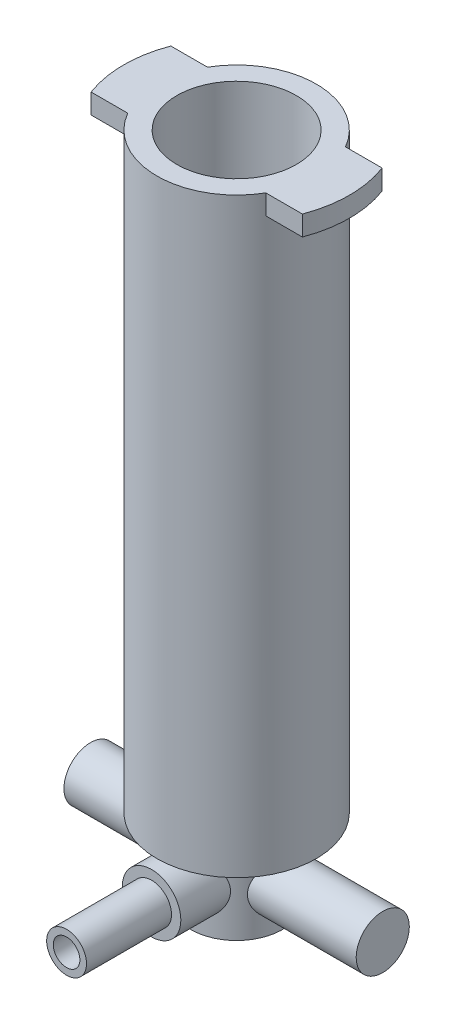
SolidWorks part; units mm, degrees
ref_plane "Front Plane" through (0, 0, 0) normal (0, 0, 1) x (1, 0, 0)
ref_plane "Top Plane" through (0, 0, 0) normal (0, 1, 0) x (1, 0, 0)
ref_plane "Right Plane" through (0, 0, 0) normal (1, 0, 0) x (0, 0, -1)
sketch "Sketch1" plane through (0, 0, 0) normal (0, 1, 0) x (1, 0, 0)
  circle A0 centre (0, 0) radius 6
extrude "Boss-Extrude1" add sketch "Sketch1" along normal blind 44.5
shell "Shell1" thickness 1.5 removed face at (0, 44.5, 6)
sketch "Sketch3" plane through (0, 0, 0) normal (0, -1, 0) x (1, 0, 0)
  circle A0 centre (0, 0) radius 3.45
extrude "Boss-Extrude3" add sketch "Sketch3" along normal blind 5.9
shell "Shell2" thickness 1.5 removed face at (0, 1.5, 4.5)
sketch "Sketch5" plane through (0, 0, 0) normal (0, 0, 1) x (1, 0, 0)
  line L0 (0, -5.9) -> (0, 0) construction
  circle A0 centre (0, -2.7032) radius 2.2
extrude "Boss-Extrude4" add sketch "Sketch5" along normal blind 6.4
sketch "Sketch6" plane through (0, 0, 6.4) normal (0, 0, 1) x (1, 0, 0)
  circle A0 centre (0, -2.7032) radius 1.5
extrude "Boss-Extrude5" add sketch "Sketch6" along normal blind 6.4
sketch "Sketch7" plane through (0, 0, 12.8) normal (0, 0, 1) x (1, 0, 0)
  circle A0 centre (0, -2.7032) radius 1
extrude "Cut-Extrude1" cut sketch "Sketch7" against normal blind 12.4
sketch "Sketch8" plane through (0, -4.4, 0) normal (0, 1, 0) x (1, 0, 0)
  circle A0 centre (0, 0) radius 1.95
extrude "Cut-Extrude2" cut sketch "Sketch8" along normal through all
sketch "Sketch9" plane through (0, 0, 0) normal (1, 0, 0) x (0, 0, -1)
  line L0 (0, 0) -> (0, -5.869) construction
  circle A0 centre (0, -2.9345) radius 2
extrude "Boss-Extrude6" add sketch "Sketch9" along normal blind 11
sketch "Sketch10" plane through (0, -4.4, 0) normal (0, 1, 0) x (1, 0, 0)
  line L0 (0, 1.95) -> (0, -2) construction
  circle A0 centre (0, -0.025) radius 1.975
extrude "Cut-Extrude3" cut sketch "Sketch10" along normal through all contours A0
sketch "Sketch11" plane through (0, 0, 12.8) normal (0, 0, 1) x (1, 0, 0)
  circle A0 centre (0, -2.7032) radius 1
extrude "Cut-Extrude4" cut sketch "Sketch11" against normal blind 12
mirror "Mirror5" about plane through (0, 0, 0) normal (1, 0, 0) of bodies 111
sketch "Sketch13" plane through (0, 44.5, 0) normal (0, 1, 0) x (1, 0, 0)
  line L0 (-5.1962, -3) -> (-7.953, -3)
  line L1 (-5.1962, 3) -> (-7.953, 3)
  line L3 (0, 1.1598) -> (0, 0.6036) construction
  line L4 (5.1962, -3) -> (7.953, -3)
  line L5 (5.1962, 3) -> (7.953, 3)
  arc A0 (-7.953, 3) -> (-7.953, -3) centre (0, 0) ccw
  arc A1 (-5.1962, -3) -> (-5.1962, 3) centre (0, 0) cw
  arc A3 (7.953, 3) -> (7.953, -3) centre (0, 0) cw
  arc A4 (5.1962, -3) -> (5.1962, 3) centre (0, 0) ccw
extrude "Boss-Extrude8" add sketch "Sketch13" against normal blind 1.5
